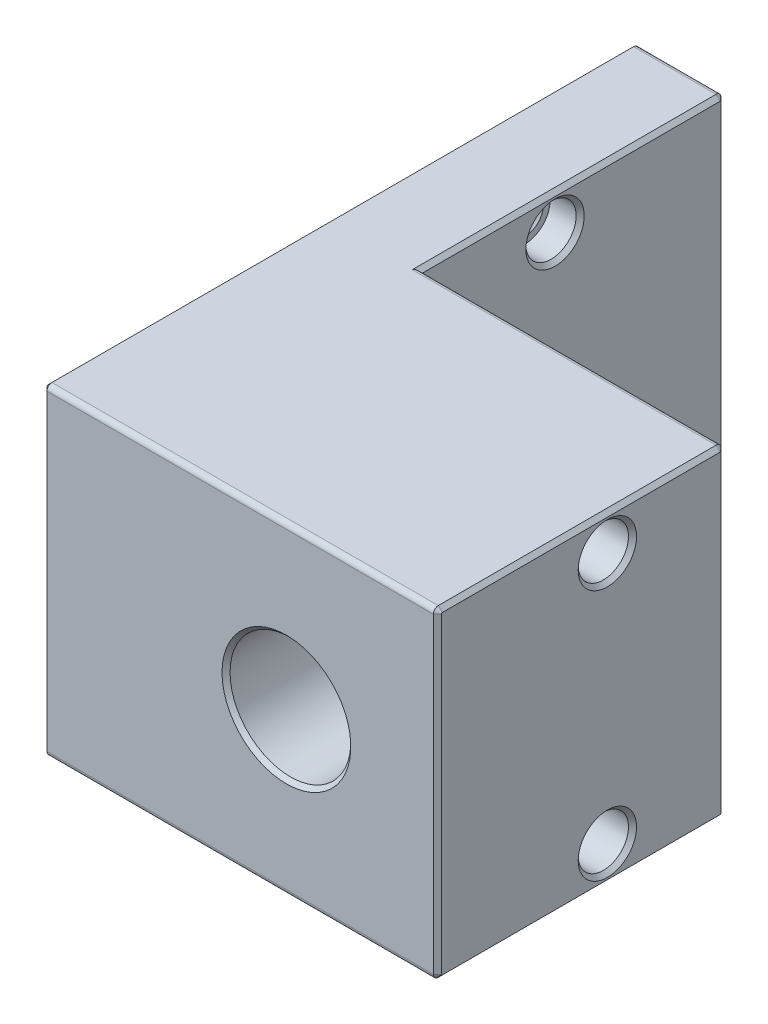
SolidWorks part; units mm, degrees
ref_plane "Front Plane" through (0, 0, 0) normal (1, 0, 0) x (0, 1, 0)
ref_plane "Top Plane" through (0, 0, 0) normal (0, 0, 1) x (0, 1, 0)
ref_plane "Right Plane" through (0, 0, 0) normal (0, 1, 0) x (-1, 0, 0)
sketch "Sketch1" plane through (0, 0, 0) normal (1, 0, 0) x (0, 1, 0)
  line L0 (-16, 0.8) -> (16, 0.8)
  line L1 (-16, -29.4) -> (16, -29.4)
  line L2 (-16, -29.4) -> (-16, 29.4)
  line L3 (-16, 29.4) -> (16, 29.4)
  line L4 (16, -29.4) -> (16, 29.4)
  line L5 (-16, -29.4) -> (16, 29.4) construction
  line L6 (-16, 29.4) -> (16, -29.4) construction
  line L7 (12.5, -12.5) -> (-12.5, -12.5) construction
  line L8 (12.5, -12.5) -> (12.5, 12.5) construction
  line L9 (12.5, 12.5) -> (-12.5, 12.5) construction
  line L10 (-12.5, -12.5) -> (-12.5, 12.5) construction
  line L11 (12.5, -12.5) -> (-12.5, 12.5) construction
  line L12 (12.5, 12.5) -> (-12.5, -12.5) construction
  circle A0 centre (-12.5, 12.5) radius 1.45
  circle A1 centre (12.5, 12.5) radius 1.45
  circle A2 centre (12.5, -12.5) radius 1.45
  circle A3 centre (-12.5, -12.5) radius 1.45
  circle A4 centre (-12.5, 12.5) radius 2.5
  circle A5 centre (12.5, 12.5) radius 2.5
  circle A6 centre (12.5, -12.5) radius 2.5
  circle A7 centre (-12.5, -12.5) radius 2.5
  point P0 (0, 0)
  point P6 (0, 0)
  dimension "D4" = 2.9
  dimension "D6" = 5
  dimension "D1" = 58.8
  dimension "D2" = 32
  dimension "D3" = 25
  dimension "D5" = 30.2
extrude "Boss-Extrude1" add sketch "Sketch1" against normal blind 6 contours L0 L4 L3 L2 A5 A4 | L1 L4 L0 L2 A7 A6 | A4 A0 | A5 A1 | A6 A2 | A7 A3 region at (0, 0, 15.2166) region at (0, 0, -14.3762) region at (0, -14.9293, 12.5) region at (0, 10.0707, 12.5) region at (0, 10.0707, -12.5) region at (0, -14.9293, -12.5)
extrude "Boss-Extrude2" add sketch "Sketch1<4>" along normal blind 3 contours L0 L4 L3 L2 A5 A4 | L1 L4 L0 L2 A7 A6 | A5 A1 | A4 A0 region at (0, 0, 15.2166) region at (0, 0, -14.3762) region at (0, -14.9293, 12.5) region at (0, 10.0707, 12.5)
sketch "Sketch1<4>" plane through (0, 0, 0) normal (1, 0, 0) x (0, 1, 0) same geometry as "Sketch1"
extrude "Boss-Extrude3" add sketch "Sketch1<5>" along normal blind 30.2 from surface contours L0 L4 L3 L2 A5 A4 | A4 A0 | A5 A1 region at (0, 0, 15.2166) region at (0, -14.9293, 12.5) region at (0, 10.0707, 12.5) starting at face at (3, 0, 0)
sketch "Sketch1<5>" plane through (0, 0, 0) normal (1, 0, 0) x (0, 1, 0) same geometry as "Sketch1"
sketch "Sketch2" plane through (0, 0, 0.8) normal (0, 0, -1) x (1, 0, 0)
  line L0 (33.2, -16) -> (3, -16) construction
  line L1 (33.2, 16) -> (3.2, 16)
  line L2 (33.2, 16) -> (33.2, -16)
  line L3 (33.2, -16) -> (3.2, -16)
  line L4 (3.2, 16) -> (3.2, -16)
  line L5 (18.2, 16) -> (18.2, -16) construction
  circle A0 centre (18.2, 0) radius 3.2
  circle A1 centre (18.2, 0) radius 6
  dimension "D2" = 6.4
  dimension "D3" = 12
  dimension "D1" = 30
extrude "Cut-Extrude1" cut sketch "Sketch2" against normal through all contours A0 L5 | L5 A0 region at (19.5581, 0, 0.8) region at (16.8419, 0, 0.8)
extrude "Cut-Extrude2" cut sketch "Sketch2<3>" against normal through all from offset 18 contours A1 L5 A0 | L5 A1 A0 region at (22.3478, -4.1478, 0.8) region at (18.0658, -4.6, 0.8) offset against normal yes
sketch "Sketch2<3>" plane through (0, 0, 0.8) normal (0, 0, -1) x (1, 0, 0) same geometry as "Sketch2"
extrude "Cut-Extrude3" cut sketch "Sketch1<6>" against normal blind 7.2 from surface contours A4 A0 | A5 A1 region at (0, -14.9293, 12.5) region at (0, 10.0707, 12.5) starting at face at (33.2, 0, 15.1)
sketch "Sketch1<6>" plane through (0, 0, 0) normal (1, 0, 0) x (0, 1, 0) same geometry as "Sketch1"
fillet "Fillet1" radius 0.5 6 edges at (13.6, 16, 29.4) (13.6, -16, 29.4) (18.1, 16, 0.8) (18.1, -16, 0.8) (-1.5, 16, -29.4) (-1.5, -16, -29.4)
chamfer "Chamfer1" distance 0.4 angle 45 36 edges at (-6, -12.5, -13.95) (-6, 12.5, -13.95) (-6, 12.5, 11.05) (-6, -12.5, 11.05) (-6, -15.8536, 29.2536) (-6, -16, 0) (-6, -15.8536, -29.2536) (-6, 0, -29.4) (-6, 15.8536, -29.2536) (-6, 16, 0) (-6, 15.8536, 29.2536) (-6, 0, 29.4) (33.2, 15.8536, 0.9464) (33.2, 0, 0.8) (33.2, -15.8536, 0.9464) (33.2, -16, 15.1) (33.2, -15.8536, 29.2536) (33.2, 0, 29.4) (33.2, 15.8536, 29.2536) (33.2, 16, 15.1) (15, 0, 18.8) (12.2, 0, 29.4) (3, -16, -13.8) (3, 16, -13.8) (3, -15.8536, -29.2536) (3, 15.8536, -29.2536) (3, 0, -29.4) (0, 12.5, -13.95) (0, -12.5, -13.95) (3, -12.5, -15) (3, 12.5, -15) (15, 0, 0.8) (33.2, -12.5, 15) (33.2, 12.5, 15) (26, -12.5, 13.95) (26, 12.5, 13.95)
